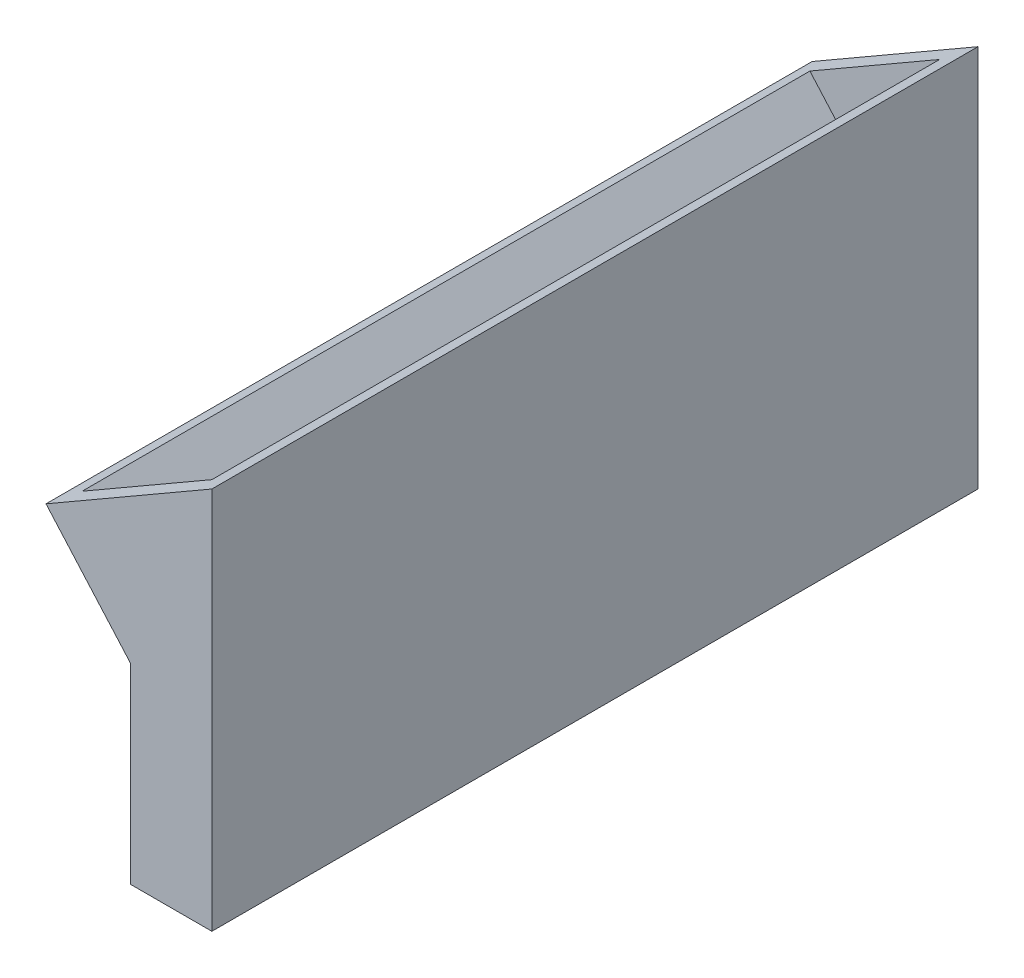
SolidWorks part; units mm, degrees
ref_plane "Front Plane" through (0, 0, 0) normal (0, 0, 1) x (1, 0, 0)
ref_plane "Top Plane" through (0, 0, 0) normal (0, 1, 0) x (1, 0, 0)
ref_plane "Right Plane" through (0, 0, 0) normal (1, 0, 0) x (0, 0, -1)
sketch "Sketch2" plane through (0, 0, 0) normal (0, 0, 1) x (1, 0, 0)
  line L0 (0, 0) -> (0, 500)
  line L1 (0, 500) -> (-259.8076, 350)
  line L2 (-259.8076, 350) -> (-127.5201, 200)
  line L3 (-127.5201, 200) -> (-127.5201, 0)
  line L4 (-127.5201, 0) -> (0, 0)
  dimension "D1" = 500
  dimension "D2" = 60
  dimension "D3" = 200
  dimension "D4" = 300
  dimension "D5" = 200
extrude "Boss-Extrude1" add sketch "Sketch2" along normal mid plane 1200
shell "Shell1" thickness 30 removed face at (-129.9038, 425, 0)
sketch "Sketch3" plane through (0, 30, 0) normal (0, 1, 0) x (1, 0, 0)
  line L1 (-97.5201, 570) -> (-30, 570)
  line L2 (-97.5201, 570) -> (-97.5201, -570)
  line L3 (-97.5201, -570) -> (-30, -570)
  line L4 (-30, 570) -> (-30, -570)
extrude "Cut-Extrude1" cut sketch "Sketch3" against normal through all
sketch "Sketch4" plane through (0, 0, 0) normal (1, 0, 0) x (0, 0, -1)
  line L0 (-600, 0) -> (600, 0)
  line L1 (600, 0) -> (200, -100)
  line L2 (200, -100) -> (-200, -100)
  line L3 (-200, -100) -> (-600, 0)
  dimension "D1" = 400
  dimension "D2" = 400
  dimension "D3" = 100
extrude "Boss-Extrude2" add sketch "Sketch4" along direction (1, 0, 0) on the side against the normal up to vertex (127.5201 mm away) up to point (-127.5201, 0, -600)
shell "Shell2" thickness 30 removed face at (-63.76, 0, 0)
sketch "Sketch5" plane through (0, -70, 0) normal (0, 1, 0) x (1, 0, 0)
  line L1 (-30, 196.3068) -> (-97.5201, 196.3068)
  line L2 (-30, 196.3068) -> (-30, -196.3068)
  line L3 (-30, -196.3068) -> (-97.5201, -196.3068)
  line L4 (-97.5201, 196.3068) -> (-97.5201, -196.3068)
  line L5 (-97.5201, 196.3068) -> (-30, 196.3068) construction
  line L7 (-97.5201, -196.3068) -> (-30, -196.3068) construction
  dimension "D1" = 30
extrude "Cut-Extrude2" cut sketch "Sketch5" against normal through all
ref_plane "Plane1" through (0, 0, -600) normal (1, 0, 0) x (0, 0, -1)
sketch "Sketch6" plane through (0, 0, -600) normal (1, 0, 0) x (0, 0, -1)
  line L0 (-1200, 0) -> (-800, -100)
  line L1 (-800, -100) -> (-1200, -100)
  line L2 (-1200, -100) -> (-1200, 0)
  line L3 (-400, -100) -> (0, 0)
  line L4 (0, 0) -> (0, -100)
  line L5 (0, -100) -> (-400, -100)
extrude "Boss-Extrude3" add sketch "Sketch6" against normal up to surface (127.5201 mm away) up to face at (-127.5201, 33.3333, 0)
fillet "Fillet1" radius 40 2 edges at (-63.76, -70, 196.3068) (-63.76, -70, -196.3068)
